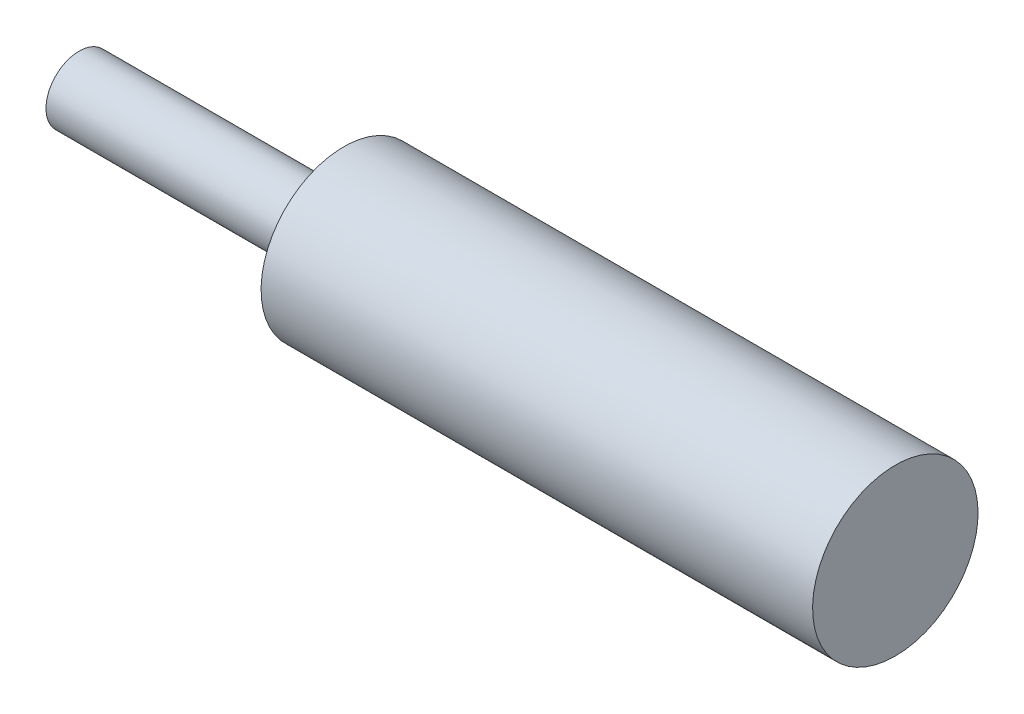
SolidWorks part; units mm, degrees
ref_plane "Front Plane" through (0, 0, 0) normal (0, 0, 1) x (1, 0, 0)
ref_plane "Top Plane" through (0, 0, 0) normal (0, 1, 0) x (1, 0, 0)
ref_plane "Right Plane" through (0, 0, 0) normal (1, 0, 0) x (0, 0, -1)
sketch "Sketch2" plane through (0, 0, 0) normal (0, 0, 1) x (1, 0, 0)
  line L0 (-37, 0) -> (37, 0)
  line L1 (-37, 0) -> (-37, 3)
  line L2 (-37, 3) -> (-13, 3)
  line L3 (-13, 3) -> (-13, 6)
  line L4 (-13, 6) -> (37, 6)
  line L5 (37, 6) -> (37, 0)
  point P5 (0, 0)
  dimension "D1" = 74
  dimension "D2" = 6
  dimension "D3" = 3
  dimension "D4" = 50
revolve "Revolve1" [suppressed] add sketch "Sketch2" angle 360 about L0
sketch "Sketch3" plane through (0, 0, 0) normal (0, 0, 1) x (1, 0, 0)
  line L0 (-37, 0) -> (37, 0)
  line L1 (-37, 0) -> (-37, 3)
  line L2 (-37, 3) -> (-13, 3)
  line L3 (-13, 3) -> (-13, 7.5)
  line L4 (-13, 7.5) -> (37, 7.5)
  line L5 (37, 7.5) -> (37, 0)
  point P4 (0, 0)
  point P10 (37, -0.811)
  dimension "D1" = 74
  dimension "D2" = 7.5
  dimension "D3" = 50
  dimension "D4" = 3
revolve "Revolve2" add sketch "Sketch3" angle 360 about L0
equation "\"mini-flipper-shaft-diameter\"= 26mm"
equation "\"mini-shaft-ring-groove-diam\"= 7.8mm"
equation "\"mini-shaft-ring-groove-width\"= 1mm"
equation "\"dtCoverPlate-DistFrom-GearCent\"= 73mm"
equation "\"wormGearShaft-L\"= \"dtCoverPlate-DistFrom-GearCent\" - 27.75 + 3.75"
equation "\"wormGearShaft-Dsmall\"= 6mm"
equation "\"wormGearShaft-Dworm\"= 12mm"
equation "\"D1@Sketch2\"=\"wormGearShaft-L\"+25"
equation "\"D2@Sketch2\"=\"wormGearShaft-Dworm\"/2"
equation "\"D3@Sketch2\"=\"wormGearShaft-Dsmall\"/2"
equation "\"D1@Sketch3\"=\"wormGearShaft-L\"+25"
equation "\"D4@Sketch3\"=\"wormGearShaft-Dsmall\"/2"
equation "\"D2@Sketch3\"=\"wormGearShaft-Dworm\"/2 + 3/2"
